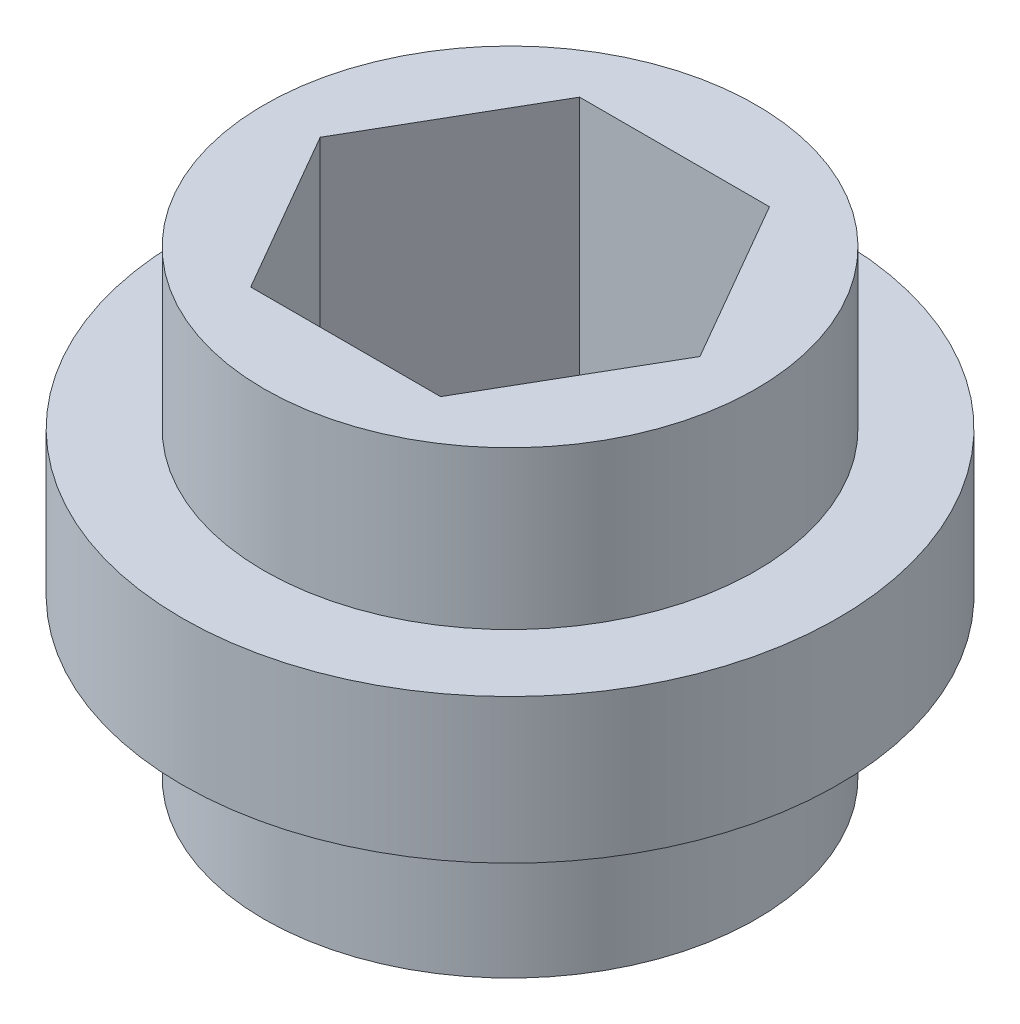
SolidWorks part; units mm, degrees
ref_plane "Front Plane" through (0, 0, 0) normal (0, 0, 1) x (1, 0, 0)
ref_plane "Top Plane" through (0, 0, 0) normal (0, 1, 0) x (1, 0, 0)
ref_plane "Right Plane" through (0, 0, 0) normal (1, 0, 0) x (0, 0, -1)
sketch "Sketch1" plane through (0, 0, 0) normal (0, 1, 0) x (1, 0, 0)
  line L0 (-2.894, -5.0125) -> (2.894, -5.0125)
  line L1 (2.894, -5.0125) -> (5.7879, 0)
  line L2 (5.7879, 0) -> (2.894, 5.0125)
  line L3 (2.894, 5.0125) -> (-2.894, 5.0125)
  line L4 (-2.894, 5.0125) -> (-5.7879, 0)
  line L5 (-5.7879, 0) -> (-2.894, -5.0125)
  circle A0 centre (0, 0) radius 7.5
  circle A1 centre (0, 0) radius 10
  point P7 (0, 0)
  point P9 (0, 5.0125)
  dimension "D3" = 15
  dimension "D4" = 20
  dimension "D1" = 120
  dimension "D2" = 10.025
extrude "Boss-Extrude1" add sketch "Sketch1" against normal mid plane 14 contours A0 L5 L4 L3 L2 L1 L0 region at (-7.2879, 0, 0)
extrude "Boss-Extrude2" add sketch "Sketch1<3>" along normal mid plane 4.4 contours A1 A0 | A0 L5 L4 L3 L2 L1 L0 region at (-7.2879, 0, 0) region at (-9.7172, 0, 0)
sketch "Sketch1<3>" plane through (0, 0, 0) normal (0, 1, 0) x (1, 0, 0) same geometry as "Sketch1"
ref_axis "Axis1" through (0, 0, 0) along (0, 1, 0)
